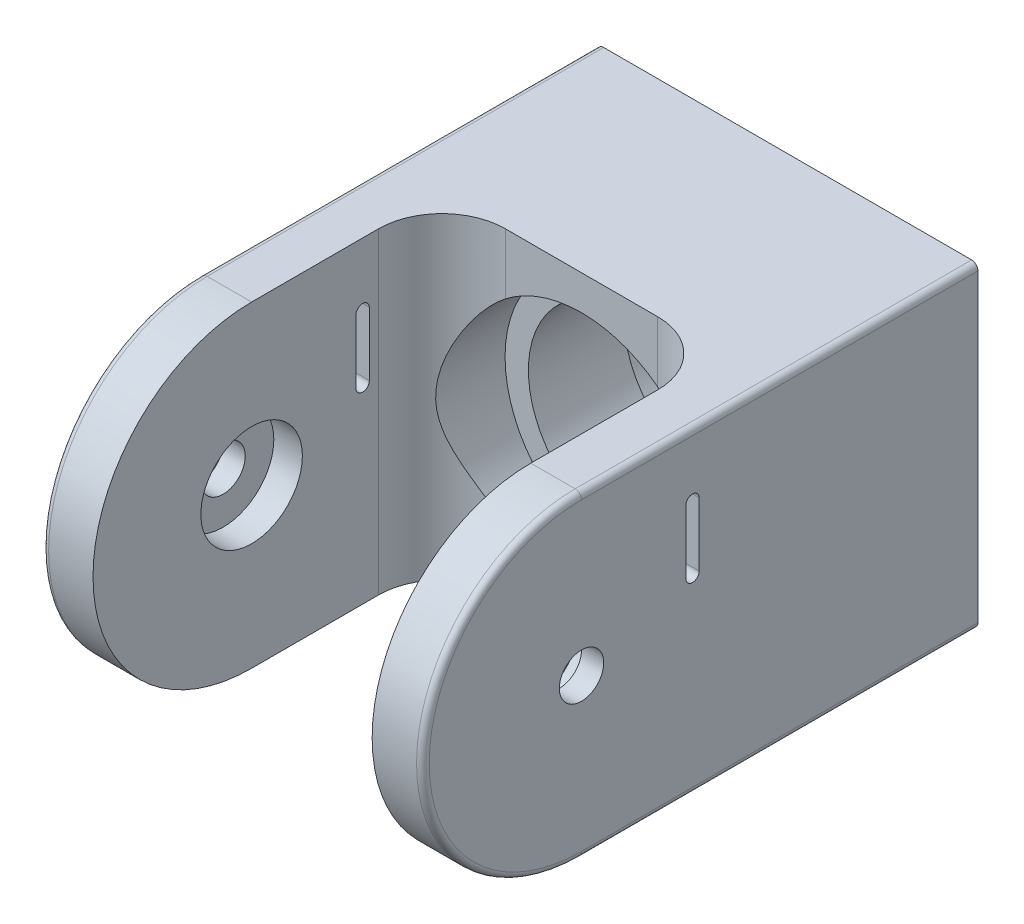
SolidWorks part; units mm, degrees
ref_plane "Front Plane" through (0, 0, 0) normal (0, 0, 1) x (1, 0, 0)
ref_plane "Top Plane" through (0, 0, 0) normal (0, 1, 0) x (1, 0, 0)
ref_plane "Right Plane" through (0, 0, 0) normal (1, 0, 0) x (0, 0, -1)
sketch "Sketch1" plane through (0, 0, 0) normal (0, 0, 1) x (1, 0, 0)
  circle A2 centre (0, 0) radius 31.75
  circle A4 centre (0, 0) radius 39.1
  circle A5 centre (0, 0) radius 38.1 construction
  dimension "D1" = 1
  dimension "D2" = 63.5
extrude "Centre Hole for L2" add sketch "Sketch1" along normal blind 30 contours A4 | A2
sketch "Sketch2" plane through (0, 0, 30) normal (0, 0, 1) x (1, 0, 0)
  line L0 (0, 48.4974) -> (0, 0) construction
  line L5 (-60, 50) -> (-60, -50)
  line L12 (0, 0) -> (72.986, 0) construction
  line L16 (-60, 50) -> (60, 50)
  line L17 (60, 50) -> (60, -50)
  line L18 (-60, -50) -> (60, -50)
  circle A2 centre (0, 0) radius 39.1
  circle A3 centre (0, 0) radius 39.1 construction
  point P13 (0, 50)
  dimension "D1" = 60
  dimension "D2" = 100
extrude "Main Structure" add sketch "Sketch2" along normal blind 75 and the other way blind 50 separate body contours L5 L18 L17 L16 A2
sketch "Sketch3" plane through (-60, 0, 0) normal (-1, 0, 0) x (0, 0, 1)
  line L0 (105, 50) -> (105, -50) construction
  line L1 (105, 50) -> (105, -50)
  line L2 (-20, 50) -> (105, 50) construction
  line L3 (-20, -50) -> (105, -50) construction
  line L4 (-20, 50) -> (105, 50) construction
  arc A0 (105, 50) -> (105, -50) centre (105, 0) cw
  point P3 (0, 0)
  point P4 (0, 0)
  point P5 (0, 0)
  point P7 (0, 0)
  point P11 (0, 0)
extrude "Bearing Curve" add sketch "Sketch3" against normal blind 16 contours A0 L1
mirror "Upright Mirror" about plane through (0, 0, 0) normal (1, 0, 0) of "Bearing Curve"
sketch "Sketch6" plane through (-60, 0, 0) normal (-1, 0, 0) x (0, 0, 1)
  circle A0 centre (105, 0) radius 7
  dimension "D1" = 14
extrude "Shaft Hole" cut sketch "Sketch6" against normal up to surface (16 mm away) up to face at (-44, 0, 130)
sketch "Sketch4" plane through (0, 50, 0) normal (0, 1, 0) x (1, 0, 0)
  line L0 (0, -105) -> (0, 20) construction
  line L3 (-44, -105) -> (-44, -65)
  line L6 (44, -105) -> (44, -65)
  line L7 (-60, 20) -> (60, 20) construction
  line L8 (-44, -105) -> (44, -105) construction
  line L9 (-24, -45) -> (24, -45)
  line L10 (-44, -105) -> (44, -105)
  arc A0 (-44, -65) -> (-24, -45) centre (-24, -65) cw
  arc A1 (44, -65) -> (24, -45) centre (24, -65) ccw
  point P4 (0, 0)
  point P5 (0, 0)
  point P17 (0, -105)
  dimension "D2" = 20
  dimension "D1" = 65
extrude "Wrist Cutout" cut sketch "Sketch4" against normal through all
sketch "Sketch9" plane through (-44, 0, 0) normal (1, 0, 0) x (0, 0, -1)
  circle A0 centre (-105, 0) radius 16
  dimension "D1" = 32
extrude "Bearing" cut sketch "Sketch9" against normal blind 9
mirror "Bearing Mirror" about plane through (0, 0, 0) normal (1, 0, 0) of "Bearing", "Shaft Hole"
fillet "Fillet1" radius 2 6 edges at (-60, 50, 42.5) (-60, -50, 42.5) (60, -50, 42.5) (60, 50, 42.5) (-60, 0, 155) (60, 0, 155)
sketch "Sketch14" plane through (-60, 0, 0) normal (-1, 0, 0) x (0, 0, 1)
  line L0 (70, 30) -> (70, 10) construction
  line L1 (72.1, 30) -> (72.1, 10)
  line L2 (67.9, 30) -> (67.9, 10)
  arc A0 (72.1, 30) -> (67.9, 30) centre (70, 30) ccw
  arc A1 (67.9, 10) -> (72.1, 10) centre (70, 10) ccw
  point P2 (70, 20)
  dimension "D1" = 4.2
  dimension "D2" = 20
  dimension "D3" = 10
  dimension "D4" = 70
extrude "Tensioner Slot" cut sketch "Sketch14" against normal up to surface (16 mm away) up to face at (-44, 0, 89)
mirror "Mirror9" about plane through (0, 0, 0) normal (1, 0, 0) of "Tensioner Slot"
